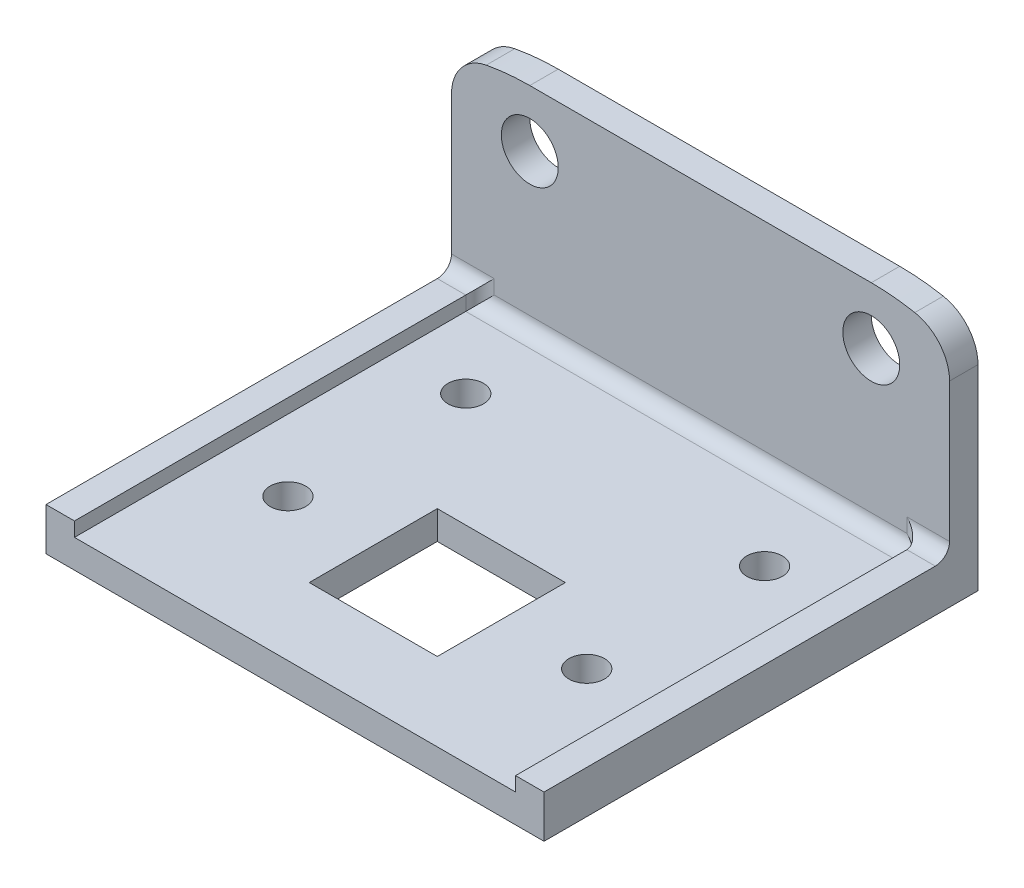
SolidWorks part; units mm, degrees
ref_plane "Front Plane" through (0, 0, 0) normal (0, 0, 1) x (1, 0, 0)
ref_plane "Top Plane" through (0, 0, 0) normal (0, 1, 0) x (1, 0, 0)
ref_plane "Right Plane" through (0, 0, 0) normal (1, 0, 0) x (0, 0, -1)
sketch "Sketch1" plane through (0, 0, 0) normal (0, 1, 0) x (1, 0, 0)
  line L0 (12.5, 24) -> (12.5, 0) construction
  line L1 (0, 0) -> (25, 0) construction
  line L2 (0, 0) -> (0, 24) construction
  line L3 (0, 24) -> (25, 24) construction
  line L4 (25, 0) -> (25, 24) construction
  line L5 (8.5, 13.5) -> (16.5, 13.5) construction
  line L6 (8.5, 13.5) -> (8.5, 5.5) construction
  line L7 (8.5, 5.5) -> (16.5, 5.5) construction
  line L8 (16.5, 13.5) -> (16.5, 5.5) construction
  line L9 (0, 15.75) -> (25, 15.75) construction
  circle A0 centre (2, 22) radius 1 construction
  circle A4 centre (23, 22) radius 1 construction
  circle A5 centre (23, 9.5) radius 1 construction
  circle A6 centre (2, 9.5) radius 1 construction
  point P11 (12.5, 13.5)
  dimension "D6" = 2
  dimension "D1" = 25
  dimension "D2" = 24
  dimension "D3" = 8
  dimension "D4" = 8
  dimension "D5" = 5.5
  dimension "D7" = 2
  dimension "D8" = 2
  dimension "D9" = 6.25
sketch "Sketch2" plane through (0, 0, 0) normal (0, 1, 0) x (1, 0, 0)
  line L0 (12.5, 24) -> (12.5, 0) construction
  line L1 (-2, -2) -> (27, -2)
  line L2 (-2, -2) -> (-2, 26)
  line L3 (-2, 26) -> (27, 26)
  line L4 (27, -2) -> (27, 26)
  line L5 (-2, -2) -> (27, 26) construction
  line L6 (-2, 26) -> (27, -2) construction
  line L7 (0, 0) -> (25, 0) construction
  line L8 (25, 0) -> (25, 24) construction
  point P0 (12.5, 12)
  dimension "D1" = 2
  dimension "D2" = 2
extrude "Boss-Extrude1" [suppressed] add sketch "Sketch2" along normal blind 1
sketch "Sketch3" plane through (0, 0, 0) normal (0, 1, 0) x (1, 0, 0)
  line L0 (16.5, 13.5) -> (16.5, 5.5) construction
  line L1 (8.5, 13.5) -> (16.5, 13.5) construction
  line L2 (8.5, 13.5) -> (8.5, 5.5) construction
  line L3 (8.5, 5.5) -> (16.5, 5.5) construction
  line L4 (16.5, 13.5) -> (16.5, 5.5) construction
  line L5 (8.5, 13.5) -> (16.5, 13.5) construction
  line L6 (8.5, 13.5) -> (8.5, 5.5) construction
  line L7 (8.5, 5.5) -> (16.5, 5.5) construction
  line L8 (8, 14) -> (8, 5)
  line L9 (8, 5) -> (17, 5)
  line L10 (17, 14) -> (17, 5)
  line L11 (8, 14) -> (17, 14)
  circle A0 centre (23, 9.5) radius 1 construction
  circle A1 centre (23, 22) radius 1 construction
  circle A2 centre (2, 22) radius 1 construction
  circle A3 centre (2, 9.5) radius 1 construction
  circle A4 centre (23, 9.5) radius 1 construction
  circle A5 centre (23, 22) radius 1 construction
  circle A6 centre (2, 22) radius 1 construction
  circle A7 centre (2, 9.5) radius 1 construction
  circle A8 centre (2, 9.5) radius 1.5
  circle A9 centre (2, 22) radius 1.5
  circle A10 centre (23, 22) radius 1.5
  circle A11 centre (23, 9.5) radius 1.5
  circle A12 centre (2, 9.5) radius 2
  dimension "D1" = 0.5
  dimension "D2" = 0.5
extrude "Cut-Extrude2" [suppressed] cut sketch "Sketch3" along normal up to next contours A8 | A9 | L5 L4 L7 L6 | A11 | A10 | L8 L9 L10 L11
sketch "Sketch6" [suppressed] plane through (0, 1, 0) normal (0, 1, 0) x (1, 0, 0)
  line L0 (12.5, 24) -> (12.5, 0) construction
  line L5 (12.5, 24) -> (12.5, 12) construction
  line L6 (0, 12) -> (25, 12) construction
  line L7 (0, 0) -> (0, 24) construction
  line L8 (25, 0) -> (25, 24) construction
  circle A0 centre (2, 9.5) radius 1.5 construction
  circle A1 centre (23, 9.5) radius 1.5 construction
  circle A2 centre (23, 22) radius 1.5 construction
  circle A3 centre (2, 22) radius 1.5 construction
  circle A4 centre (2, 9.5) radius 1.5
  circle A5 centre (23, 9.5) radius 1.5
  circle A6 centre (23, 22) radius 1.5
  circle A7 centre (2, 22) radius 1.5
  circle A8 centre (2, 22) radius 2.25
  circle A9 centre (2, 9.5) radius 2.25
  circle A10 centre (23, 9.5) radius 2.25
  circle A11 centre (23, 22) radius 2.25
  point P30 (-1, 25)
  dimension "D1" = 0.75
extrude "Boss-Extrude3" [suppressed] add sketch "Sketch6" along normal blind 4
sketch "Sketch8" [suppressed] plane through (0, 5, 0) normal (0, 1, 0) x (1, 0, 0)
  line L4 (27, -2) -> (27, 26)
  line L5 (27, 26) -> (-2, 26)
  line L6 (-2, 26) -> (-2, -2)
  line L7 (-2, -2) -> (27, -2)
  line L8 (27, -2) -> (27, 26)
  line L9 (27, 26) -> (-2, 26)
  line L10 (-2, 26) -> (-2, -2)
  line L11 (-2, -2) -> (27, -2)
  dimension "D1" = 0
extrude "Boss-Extrude4" [suppressed] add sketch "Sketch8" along normal blind 1
split "Split2" [suppressed] bodies to split 105
sketch "Sketch9" plane through (0, 0, 0) normal (0, 1, 0) x (1, 0, 0)
  line L0 (25, 0) -> (25, 24) construction
  line L1 (0, 0) -> (25, 0) construction
  line L2 (0, 0) -> (0, 24) construction
  line L3 (0, 24) -> (25, 24) construction
  line L4 (25, 0) -> (25, 24) construction
  line L5 (0, 0) -> (25, 0) construction
  line L6 (0, 0) -> (0, 24) construction
  line L7 (0, 24) -> (25, 24) construction
  line L8 (30, -0.5) -> (30, 30)
  line L9 (-5, 30) -> (30, 30)
  line L10 (-5, -0.5) -> (-5, 30)
  line L11 (-5, -0.5) -> (30, -0.5)
  line L12 (16.5, 13.5) -> (16.5, 5.5) construction
  line L13 (8.5, 13.5) -> (16.5, 13.5) construction
  line L14 (8.5, 5.5) -> (16.5, 5.5) construction
  line L15 (8.5, 13.5) -> (8.5, 5.5) construction
  line L16 (16.5, 13.5) -> (16.5, 5.5) construction
  line L17 (8.5, 13.5) -> (16.5, 13.5) construction
  line L18 (8.5, 5.5) -> (16.5, 5.5) construction
  line L19 (8.5, 13.5) -> (8.5, 5.5) construction
  line L20 (17, 14) -> (17, 5)
  line L21 (8, 5) -> (17, 5)
  line L22 (8, 14) -> (8, 5)
  line L23 (8, 14) -> (17, 14)
  dimension "D3" = 6
  dimension "D1" = 5
  dimension "D4" = 5
  dimension "D5" = 0.5
  dimension "D2" = 0.5
extrude "Boss-Extrude5" add sketch "Sketch9" along normal blind 2
sketch "Sketch10" plane through (0, 2, 0) normal (0, 1, 0) x (1, 0, 0)
  line L0 (25, 0) -> (25, 24) construction
  line L1 (0, 0) -> (25, 0) construction
  line L2 (0, 0) -> (0, 24) construction
  line L3 (0, 24) -> (25, 24) construction
  line L4 (25, 0) -> (25, 24) construction
  line L5 (0, 0) -> (25, 0) construction
  line L6 (0, 0) -> (0, 24) construction
  line L7 (0, 24) -> (25, 24) construction
  line L8 (28, -0.5) -> (28, 28)
  line L9 (-3, 28) -> (28, 28)
  line L10 (-3, -0.5) -> (-3, 28)
  line L12 (-5, -0.5) -> (30, -0.5)
  line L13 (30, -0.5) -> (30, 30)
  line L14 (30, 30) -> (-5, 30)
  line L15 (-5, 30) -> (-5, -0.5)
  line L16 (-5, -0.5) -> (-3, -0.5)
  line L17 (30, -0.5) -> (30, 30)
  line L18 (30, 30) -> (-5, 30)
  line L19 (-5, 30) -> (-5, -0.5)
  line L20 (28, -0.5) -> (30, -0.5)
  dimension "D2" = 2
  dimension "D3" = 2
  dimension "D4" = 2
  dimension "D1" = 0
extrude "Boss-Extrude6" add sketch "Sketch10" along normal blind 1
sketch "Sketch12" plane through (0, 2, 0) normal (0, 1, 0) x (1, 0, 0)
  circle A0 centre (23, 9.5) radius 1 construction
  circle A1 centre (23, 22) radius 1 construction
  circle A2 centre (2, 22) radius 1 construction
  circle A3 centre (2, 9.5) radius 1 construction
  circle A4 centre (23, 9.5) radius 1 construction
  circle A5 centre (23, 22) radius 1 construction
  circle A6 centre (2, 22) radius 1 construction
  circle A7 centre (2, 9.5) radius 1 construction
  circle A8 centre (2, 22) radius 1.25
  circle A9 centre (2, 9.5) radius 1.25
  circle A10 centre (23, 9.5) radius 1.25
  circle A11 centre (23, 22) radius 1.25
  dimension "D1" = 0.25
extrude "Cut-Extrude4" cut sketch "Sketch12" against normal up to next
ref_plane "Plane1" through (12.5, 0, 0) normal (1, 0, 0) x (0, 0, -1)
sketch "Sketch13" plane through (0, 0, -30) normal (0, 0, -1) x (-1, 0, 0)
  line L0 (-30, 3) -> (-30, 13.7648)
  line L2 (-12.5, 3) -> (-12.5, 19.0213) construction
  line L3 (-30, 3) -> (5, 3) construction
  line L4 (5, 3) -> (5, 13.7648)
  line L5 (-30, 3) -> (5, 3)
  line L6 (-24.5, 17) -> (-0.5, 17)
  circle A0 centre (-24.5, 13) radius 2
  circle A1 centre (-0.5, 13) radius 2
  arc A2 (-24.5, 17) -> (-27.5594, 16.7122) centre (-24.5, 0.5933) ccw
  arc A3 (-0.5, 17) -> (2.5594, 16.7122) centre (-0.5, 0.5933) cw
  arc A4 (2.5594, 16.7122) -> (5, 13.7648) centre (2, 13.7648) cw
  arc A5 (-27.5594, 16.7122) -> (-30, 13.7648) centre (-27, 13.7648) ccw
  point P9 (-12.5, 19)
  point P17 (-12.5, 17)
  point P21 (5, 16.0507)
  point P24 (-30, 16.0507)
  dimension "D3" = 4
  dimension "D7" = 2
  dimension "D2" = 3
  dimension "D1" = 17.5
  dimension "D4" = 10
  dimension "D5" = 12
  dimension "D6" = 2
extrude "Boss-Extrude7" add sketch "Sketch13" against normal up to surface (2 mm away) up to face at (12.5, 2.5, -28)
sketch "Sketch14" plane through (30, 0, 0) normal (1, 0, 0) x (0, 0, -1)
  line L0 (-0.5, 3) -> (28, 3) construction
  line L1 (28, 13.7648) -> (28, 3) construction
  line L2 (23, 3) -> (28, 3)
  line L3 (28, 3) -> (28, 6.5)
  line L5 (28, 15) -> (28, 11) construction
  line L6 (28, 15) -> (28, 11) construction
  arc A0 (23, 3) -> (28, 6.5) centre (21.5712, 10.3626) ccw
  dimension "D1" = 5
  dimension "D2" = 7.5
  dimension "D3" = 3.5
extrude "Boss-Extrude8" [suppressed] add sketch "Sketch14" against normal up to surface (33 mm away) up to face at (-5, 5.5883, -19.1667)
sketch "Sketch15" [suppressed] plane through (0, 0, 4) normal (0, 0, 1) x (1, 0, 0)
  line L0 (-3, 4) -> (-3, 2) construction
  line L1 (-3, 4) -> (-3, 2) construction
  line L2 (28, 4) -> (28, 2) construction
  line L3 (28, 4) -> (28, 2) construction
  line L4 (-4, 7.5) -> (29, 7.5) construction
  line L5 (-3, 4) -> (28, 4) construction
  line L6 (-3, 4) -> (-3, 7.5) construction
  line L7 (-3, 7.5) -> (28, 7.5) construction
  line L8 (28, 4) -> (28, 7.5) construction
  line L9 (-4, 7.5) -> (29, 7.5) construction
  line L10 (-3, 4) -> (28, 4) construction
  line L11 (4.5993, -2.5) -> (4.5993, -2.5)
  line L12 (4.5993, -2.5) -> (28, -2.5)
  line L13 (-3.01, 3.99) -> (28.01, 3.99)
  line L14 (28.01, 3.99) -> (28.01, 7.51)
  line L15 (-3.01, 7.51) -> (28.01, 7.51)
  line L16 (-3.01, 3.99) -> (-3.01, 7.51)
  line M8 (-1, 2) -> (-1, 4)
  line M9 (-1, 4) -> (-4, 4)
  line M13 (29, 4) -> (26, 4)
  line M14 (26, 4) -> (26, 2)
  dimension "D1" = 10
  dimension "D2" = 0.01
extrude "Cut-Extrude7" [suppressed] cut sketch "Sketch15" against normal up to surface (31 mm away) contours L16 L13 L14 L15 M9 M8 M14 M13 up to face at (12.5, 9.3314, -28)
fillet "Fillet1" radius 1 5 edges at (12.5, 2, -28) (-3, 2.5, -28) (-4, 3, -28) (28, 2.5, -28) (29, 3, -28)
